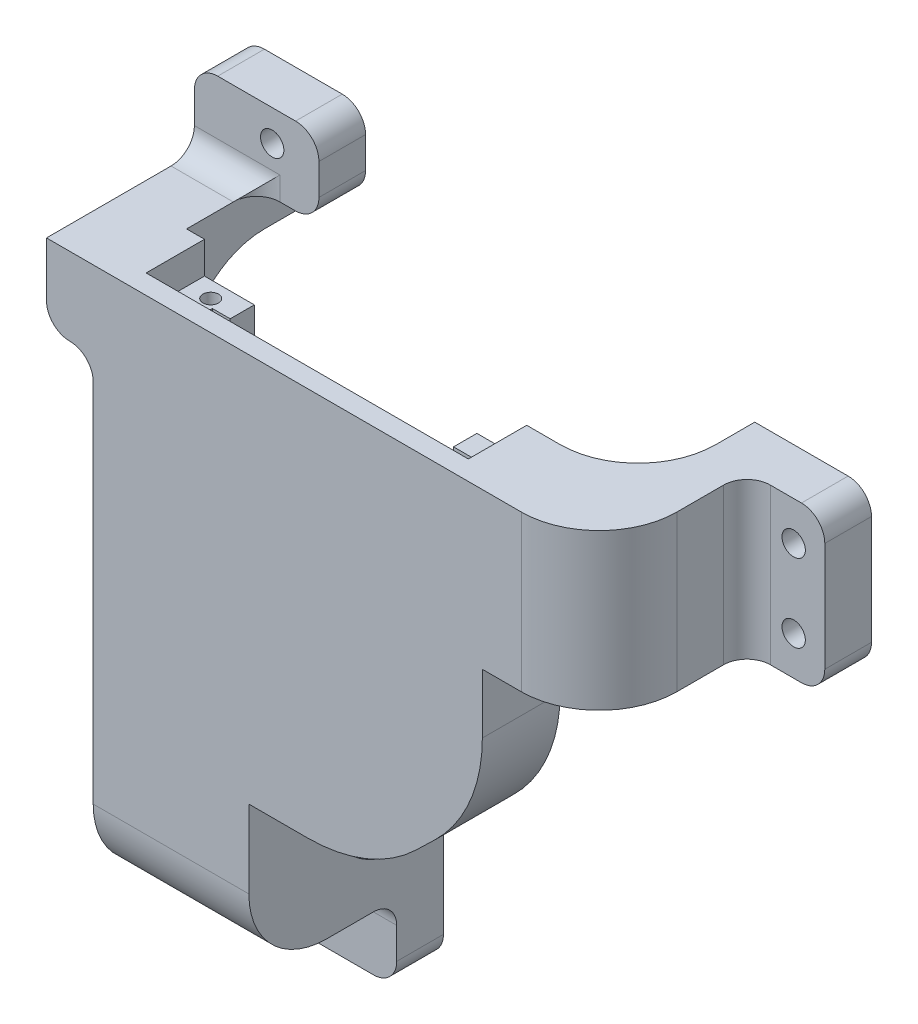
SolidWorks part; units mm, degrees
material "Polylactide (PLA)"
ref_plane "Front Plane" through (0, 0, 0) normal (0, 0, 1) x (1, 0, 0)
ref_plane "Top Plane" through (0, 0, 0) normal (0, 1, 0) x (1, 0, 0)
ref_plane "Right Plane" through (0, 0, 0) normal (1, 0, 0) x (0, 0, -1)
sketch "Sketch1" plane through (0, 0, 0) normal (0, 1, 0) x (1, 0, 0)
  line L0 (0, 0) -> (82.5, 0)
  line L1 (0, 0) -> (10, 0)
  line L2 (0, 0) -> (0, 20)
  line L3 (0, 20) -> (10, 20)
  line L4 (10, 0) -> (10, 20)
extrude "Boss-Extrude2" add sketch "Sketch1" along normal blind 10 contours L1 L4 L3 L2
sketch "Sketch3" plane through (0, 0, 0) normal (0, 1, 0) x (1, 0, 0)
  line L0 (0, 0) -> (82.5, 0)
  line L1 (0, 0) -> (10, 0) construction
  line L3 (82.5, 0) -> (72.5, 0)
  line L4 (82.5, 0) -> (82.5, 20)
  line L5 (82.5, 20) -> (72.5, 20)
  line L6 (72.5, 0) -> (72.5, 20)
extrude "Boss-Extrude3" add sketch "Sketch3" along normal blind 10 separate body contours L3 L6 L5 L4
sketch "Sketch4" plane through (0, 0, 0) normal (0, 1, 0) x (1, 0, 0)
  line L0 (10, 0) -> (10, 7.5)
  line L3 (10, 0) -> (10, 20) construction
  line L4 (72.5, 0) -> (72.5, 20) construction
  line L5 (10, 7.5) -> (72.5, 7.5)
  line L6 (10, 7.5) -> (10, 12.5)
  line L7 (10, 12.5) -> (72.5, 12.5)
  line L8 (72.5, 7.5) -> (72.5, 12.5)
extrude "Boss-Extrude4" add sketch "Sketch4" along normal blind 10 contours L5 L8 L7 L6
sketch "Sketch5" plane through (10, 0, 0) normal (1, 0, 0) x (0, 0, -1)
  line L0 (12.5, 0) -> (20, 10)
  line L1 (20, 0) -> (12.5, 10)
  line L2 (0, 10) -> (20, 10) construction
  circle A0 centre (16.25, 5) radius 0.5
sketch "Sketch6" plane through (10, 0, 0) normal (1, 0, 0) x (0, 0, -1)
  circle A0 centre (16.25, 5) radius 1
extrude "Cut-Extrude1" cut sketch "Sketch6" against normal blind 10
sketch "Sketch8" plane through (10, 0, 0) normal (1, 0, 0) x (0, 0, -1)
  line L0 (7.5, 0) -> (0, 10)
  line L1 (0, 10) -> (7.5, 10)
  line L2 (0, 10) -> (20, 10) construction
  line L3 (7.5, 10) -> (0, 0)
  circle A0 centre (3.75, 5) radius 1
sketch "Sketch10" plane through (72.5, 0, 0) normal (-1, 0, 0) x (0, 0, 1)
  circle A0 centre (-16.25, 5) radius 1
extrude "Cut-Extrude3" cut sketch "Sketch10" against normal blind 10 contours A0
sketch "Sketch11" plane through (0, 0, -12.5) normal (0, 0, -1) x (-1, 0, 0)
  line L0 (0, 10) -> (-35, 10)
  line L1 (-10, 10) -> (-72.5, 10) construction
  line L2 (-35, 10) -> (-35, 20)
  line L8 (-60, 45) -> (-10, 45)
  line L9 (-60, 45) -> (-60, -5)
  line L10 (-60, -5) -> (-10, -5)
  line L11 (-10, 45) -> (-10, -5)
  line L12 (-60, 45) -> (-10, -5) construction
  line L13 (-60, -5) -> (-10, 45) construction
sketch "Sketch16" plane through (10, 0, 0) normal (1, 0, 0) x (0, 0, -1)
  circle A0 centre (-1.6096, 5.0574) radius 1
sketch "Sketch17" plane through (72.5, 0, 0) normal (-1, 0, 0) x (0, 0, 1)
  circle A0 centre (-3.75, 5) radius 1
extrude "Boss-Extrude8" add sketch "Sketch11" against normal blind 10 contours L11 L10 L9 L8
sketch "Sketch18" plane through (0, 0, 0) normal (0, 0, 1) x (1, 0, 0)
  line L1 (0, 10) -> (10, 10)
  line L2 (0, 10) -> (0, 0)
  line L3 (0, 0) -> (10, 0)
  line L4 (10, 10) -> (10, 0)
extrude "Boss-Extrude9" add sketch "Sketch18" along normal blind 6
sketch "Sketch19" plane through (10, 0, 0) normal (1, 0, 0) x (0, 0, -1)
  circle A0 centre (-1.6096, 5.0574) radius 1
sketch "Sketch20" plane through (0, 0, 0) normal (0, -1, 0) x (1, 0, 0)
  line L0 (82.5, 0) -> (82.5, -20) construction
  line L1 (72.5, -12.5) -> (82.5, -12.5)
  line L2 (72.5, -12.5) -> (72.5, -2.5)
  line L3 (72.5, -2.5) -> (82.5, -2.5)
  line L4 (82.5, -12.5) -> (82.5, -2.5)
  line L5 (0, 6) -> (0, -20) construction
  line L6 (10, -2.5) -> (0, -2.5)
  line L7 (10, -2.5) -> (10, -12.5)
  line L8 (10, -12.5) -> (0, -12.5)
  line L9 (0, -2.5) -> (0, -12.5)
extrude "Boss-Extrude10" add sketch "Sketch20" along normal blind 12
sketch "Sketch21" plane through (72.5, 0, 0) normal (-1, 0, 0) x (0, 0, 1)
  circle A0 centre (-7.3635, -7.3831) radius 1
sketch "Sketch22" plane through (10, 0, 0) normal (1, 0, 0) x (0, 0, -1)
  circle A0 centre (7.5816, -8.9099) radius 1
sketch "Sketch23" plane through (0, 0, -12.5) normal (0, 0, -1) x (-1, 0, 0)
  line L0 (-60, 45) -> (-49.3, 45)
  line L3 (-60, 45) -> (-10, 45) construction
  line L5 (-49.3, 45) -> (-20.7, 45)
  line L6 (-49.3, 45) -> (-49.3, 0)
  line L7 (-49.3, 0) -> (-20.7, 0)
  line L8 (-20.7, 45) -> (-20.7, 0)
extrude "Cut-Extrude10" cut sketch "Sketch23" against normal blind 7.5 contours L6 L7 L8 L5
sketch "Sketch24" plane through (0, 45, 0) normal (0, 1, 0) x (1, 0, 0)
  line L1 (20.7, 12.5) -> (14.3, 12.5)
  line L2 (20.7, 12.5) -> (20.7, 5)
  line L3 (20.7, 5) -> (14.3, 5)
  line L4 (14.3, 12.5) -> (14.3, 5)
  line L5 (49.3, 12.5) -> (55.7, 12.5)
  line L6 (49.3, 12.5) -> (49.3, 5)
  line L7 (49.3, 5) -> (55.7, 5)
  line L8 (55.7, 12.5) -> (55.7, 5)
extrude "Cut-Extrude11" cut sketch "Sketch24" against normal blind 4.1
sketch "Sketch25" plane through (0, 40.9, 0) normal (0, 1, 0) x (1, 0, 0)
  line L1 (49.3, 5) -> (49.3, 7)
  line L2 (49.3, 5) -> (49.3, 12.5) construction
  line L4 (49.3, 7) -> (51.6, 7)
  line L5 (49.3, 7) -> (49.3, 9.5)
  line L6 (49.3, 9.5) -> (51.6, 9.5)
  line L7 (51.6, 7) -> (51.6, 9.5)
extrude "Cut-Extrude12" cut sketch "Sketch25" against normal blind 39 contours L4 L7 L6 L5
sketch "Sketch26" plane through (0, 40.9, 0) normal (0, 1, 0) x (1, 0, 0)
  line L0 (20.7, 5) -> (20.7, 7)
  line L1 (20.7, 5) -> (20.7, 12.5) construction
  line L3 (20.7, 7) -> (18.4, 7)
  line L4 (20.7, 7) -> (20.7, 9.4)
  line L5 (20.7, 9.4) -> (18.4, 9.4)
  line L6 (18.4, 7) -> (18.4, 9.4)
extrude "Cut-Extrude13" cut sketch "Sketch26" against normal blind 41 contours L3 L6 L5 L4
sketch "Sketch27" plane through (0, 40.9, 0) normal (0, 1, 0) x (1, 0, 0)
  line L1 (14.3, 12.5) -> (17.2, 12.5)
  line L2 (14.3, 12.5) -> (14.3, 10.4)
  line L3 (14.3, 10.4) -> (17.2, 10.4)
  line L4 (17.2, 12.5) -> (17.2, 10.4)
  circle A0 centre (17.2, 10.4) radius 1
extrude "Cut-Extrude14" cut sketch "Sketch27" against normal blind 10 contours A0
sketch "Sketch28" plane through (0, 40.9, 0) normal (0, 1, 0) x (1, 0, 0)
  line L1 (55.7, 12.5) -> (52.8, 12.5)
  line L2 (55.7, 12.5) -> (55.7, 10.4)
  line L3 (55.7, 10.4) -> (52.8, 10.4)
  line L4 (52.8, 12.5) -> (52.8, 10.4)
  circle A0 centre (52.8, 10.4) radius 1
extrude "Cut-Extrude15" cut sketch "Sketch28" against normal blind 10 contours A0
sketch "Sketch30" plane through (0, 40.9, 0) normal (0, 1, 0) x (1, 0, 0)
  line L0 (17.2, 10.4) -> (52.8, 10.4)
sketch "Sketch31" plane through (0, 0, -7.5) normal (0, 0, 1) x (1, 0, 0)
  line L4 (72.5, 10) -> (60, 10)
  line L5 (60, 10) -> (60, 0)
  line L6 (60, 0) -> (72.5, 0)
  line L7 (72.5, 0) -> (72.5, 10)
  line L8 (72.5, 10) -> (60, 10)
  line L9 (60, 10) -> (60, 0)
  line L10 (60, 0) -> (72.5, 0)
  line L11 (72.5, 0) -> (72.5, 10)
  dimension "D1" = 0
extrude "Boss-Extrude11" add sketch "Sketch31" along normal blind 5 contours L11 L8 L9 L10
sketch "Sketch32" plane through (0, 0, -20) normal (0, 0, -1) x (-1, 0, 0)
  line L4 (-82.5, 0) -> (-72.5, 0)
  line L5 (-72.5, 0) -> (-72.5, 10)
  line L6 (-72.5, 10) -> (-82.5, 10)
  line L7 (-82.5, 10) -> (-82.5, 0)
  line L8 (-82.5, 0) -> (-72.5, 0)
  line L9 (-72.5, 0) -> (-72.5, 10)
  line L10 (-72.5, 10) -> (-82.5, 10)
  line L11 (-82.5, 10) -> (-82.5, 0)
  dimension "D1" = 0
extrude "Cut-Extrude16" cut sketch "Sketch32" against normal blind 7.5
sketch3d "3DSketch1"
  line L4 (10, 0, -20) -> (0, 0, -20)
  line L5 (0, 0, -20) -> (0, 10, -20)
  line L6 (0, 10, -20) -> (10, 10, -20)
  line L7 (10, 10, -20) -> (10, 0, -20)
  line L8 (10, 0, -20) -> (0, 0, -20)
  line L9 (0, 0, -20) -> (0, 10, -20)
  line L10 (0, 10, -20) -> (10, 10, -20)
  line L11 (10, 10, -20) -> (10, 0, -20)
  dimension "D1" = 0
extrude "Cut-Extrude17" cut sketch "3DSketch1" along direction (0, 0, -1) on the side of the normal blind 7.5
sketch "Sketch33" plane through (0, -12, 0) normal (0, -1, 0) x (1, 0, 0)
  line L4 (10, -12.5) -> (10, -2.5)
  line L5 (10, -2.5) -> (0, -2.5)
  line L6 (0, -2.5) -> (0, -12.5)
  line L7 (0, -12.5) -> (10, -12.5)
  line L8 (10, -12.5) -> (10, -2.5)
  line L9 (10, -2.5) -> (0, -2.5)
  line L10 (0, -2.5) -> (0, -12.5)
  line L11 (0, -12.5) -> (10, -12.5)
  dimension "D1" = 0
extrude "Boss-Extrude12" add sketch "Sketch33" along normal blind 5
sketch "Sketch34" plane through (0, -12, 0) normal (0, -1, 0) x (1, 0, 0)
  line L4 (72.5, -2.5) -> (72.5, -12.5)
  line L5 (72.5, -12.5) -> (82.5, -12.5)
  line L6 (82.5, -12.5) -> (82.5, -2.5)
  line L7 (82.5, -2.5) -> (72.5, -2.5)
  line L8 (72.5, -2.5) -> (72.5, -12.5)
  line L9 (72.5, -12.5) -> (82.5, -12.5)
  line L10 (82.5, -12.5) -> (82.5, -2.5)
  line L11 (82.5, -2.5) -> (72.5, -2.5)
  dimension "D1" = 0
extrude "Boss-Extrude13" add sketch "Sketch34" along normal blind 5
sketch "Sketch35" plane through (0, 0, 6) normal (0, 0, 1) x (1, 0, 0)
  line L4 (0, 10) -> (0, 0)
  line L5 (0, 0) -> (10, 0)
  line L6 (10, 0) -> (10, 10)
  line L7 (10, 10) -> (0, 10)
  line L8 (0, 10) -> (0, 0)
  line L9 (0, 0) -> (10, 0)
  line L10 (10, 0) -> (10, 10)
  line L11 (10, 10) -> (0, 10)
  dimension "D1" = 0
extrude "Boss-Extrude14" add sketch "Sketch35" along normal blind 3.5
sketch "Sketch36" plane through (0, 0, 0) normal (0, 0, 1) x (1, 0, 0)
  line L4 (72.5, 0) -> (82.5, 0)
  line L5 (82.5, 0) -> (82.5, 10)
  line L6 (82.5, 10) -> (72.5, 10)
  line L7 (72.5, 10) -> (72.5, 0)
  line L8 (72.5, 0) -> (82.5, 0)
  line L9 (82.5, 0) -> (82.5, 10)
  line L10 (82.5, 10) -> (72.5, 10)
  line L11 (72.5, 10) -> (72.5, 0)
  dimension "D1" = 0
extrude "Boss-Extrude15" add sketch "Sketch36" along normal blind 9.5
sketch "Sketch37" plane through (10, 0, 0) normal (1, 0, 0) x (0, 0, -1)
  line L0 (-9.5, 10) -> (2.5, 0)
  line L1 (2.5, 0) -> (-9.5, 0)
  line L2 (-9.5, 0) -> (2.5, 10)
  circle A0 centre (-3.5, 5) radius 1.25
sketch "Sketch38" plane through (10, 0, 0) normal (1, 0, 0) x (0, 0, -1)
  line L0 (2.5, -5) -> (12.5, -17)
  line L1 (12.5, -17) -> (12.5, -5)
  line L2 (12.5, -5) -> (2.5, -17)
  circle A0 centre (7.5, -11) radius 1.25
extrude "Cut-Extrude18" cut sketch "Sketch37" against normal blind 15.5 and the other way blind 90.5 contours A0
extrude "Cut-Extrude19" cut sketch "Sketch38" against normal blind 15.5 and the other way blind 88.5 contours A0
sketch "Sketch39" plane through (0, 0, -12.5) normal (0, 0, -1) x (-1, 0, 0)
  line L0 (-60, 45) -> (-60, 10) construction
  line L1 (-60, 11.6104) -> (-89.9671, 11.6104)
  line L2 (-60, 11.6104) -> (-60, -20.2254)
  line L3 (-60, -20.2254) -> (-89.9671, -20.2254)
  line L4 (-89.9671, 11.6104) -> (-89.9671, -20.2254)
  line L5 (-10, 45) -> (-10, 10) construction
  line L6 (-10, 12.6125) -> (5.6172, 12.6125)
  line L7 (-10, 12.6125) -> (-10, -19.6858)
  line L8 (-10, -19.6858) -> (5.6172, -19.6858)
  line L9 (5.6172, 12.6125) -> (5.6172, -19.6858)
extrude "Cut-Extrude20" cut sketch "Sketch39" against normal blind 36
sketch "Sketch40" plane through (10, 0, 0) normal (-1, 0, 0) x (0, 0, 1)
  line L0 (-2.5, 45) -> (-2.5, -5) construction
  line L1 (-12.5, 45) -> (-2.5, 45)
  line L2 (-12.5, 45) -> (-12.5, 35)
  line L3 (-12.5, 35) -> (-2.5, 35)
  line L4 (-2.5, 45) -> (-2.5, 35)
extrude "Boss-Extrude16" add sketch "Sketch40" along normal blind 6
sketch "Sketch41" plane through (0, -5, 0) normal (0, -1, 0) x (1, 0, 0)
  line L1 (10, -2.5) -> (30, -2.5)
  line L2 (10, -2.5) -> (10, -12.5)
  line L3 (10, -12.5) -> (30, -12.5)
  line L4 (30, -2.5) -> (30, -12.5)
extrude "Boss-Extrude17" add sketch "Sketch41" along normal blind 20
sketch "Sketch43" plane through (60, 0, 0) normal (1, 0, 0) x (0, 0, -1)
  line L0 (2.5, 45) -> (12.5, 45) construction
  line L1 (2.5, 25) -> (12.5, 25)
  line L2 (2.5, 25) -> (2.5, 45)
  line L3 (2.5, 45) -> (12.5, 45)
  line L4 (12.5, 25) -> (12.5, 45)
  line L5 (2.5, 45) -> (2.5, -5) construction
  line L6 (12.5, 45) -> (12.5, -5) construction
extrude "Boss-Extrude18" add sketch "Sketch43" along normal blind 15
sketch "Sketch44" plane through (0, 0, -12.5) normal (0, 0, -1) x (-1, 0, 0)
  line L1 (-75, 45) -> (-70, 45)
  line L2 (-75, 45) -> (-75, 25)
  line L3 (-75, 25) -> (-70, 25)
  line L4 (-70, 45) -> (-70, 25)
  line L6 (-30, -25) -> (-10, -25)
  line L7 (-30, -25) -> (-30, -20)
  line L8 (-30, -20) -> (-10, -20)
  line L9 (-10, -25) -> (-10, -20)
  line L10 (-4, 45) -> (-12, 45)
  line L11 (-4, 45) -> (-4, 40)
  line L12 (-4, 40) -> (-12, 40)
  line L13 (-12, 45) -> (-12, 40)
extrude "Boss-Extrude19" add sketch "Sketch44" along normal blind 13
sketch "Sketch45" plane through (0, 0, -25.5) normal (0, 0, -1) x (-1, 0, 0)
  line L0 (-10, -20) -> (-30, -20) construction
  line L1 (-70, 45) -> (-85, 45)
  line L2 (-70, 45) -> (-70, 25)
  line L3 (-70, 25) -> (-85, 25)
  line L4 (-85, 45) -> (-85, 25)
  line L5 (-30, -20) -> (-10, -20)
  line L6 (-30, -20) -> (-30, -35)
  line L7 (-30, -35) -> (-10, -35)
  line L8 (-10, -20) -> (-10, -35)
  line L10 (-12, 40) -> (-4, 40)
  line L11 (-12, 40) -> (-12, 55)
  line L12 (-12, 55) -> (-4, 55)
  line L13 (-4, 40) -> (-4, 55)
extrude "Boss-Extrude20" add sketch "Sketch45" against normal blind 4
sketch "Sketch47" plane through (0, 0, -21.5) normal (0, 0, 1) x (1, 0, 0)
  line L0 (30, -35) -> (10, -35) construction
  line L1 (10, -35) -> (10, -25) construction
  line L2 (85, 25) -> (75, 25) construction
  line L3 (85, 45) -> (85, 25) construction
  circle A0 centre (15, -31) radius 1.5
  circle A2 centre (81, 30) radius 1.5
  circle A3 centre (81, 40) radius 1.5
  dimension "D1" = 4
  dimension "D5" = 5
  dimension "D2" = 5
  dimension "D6" = 4
  dimension "D7" = 10
  dimension "D8" = 0
sketch "Sketch49" plane through (0, 0, -25.5) normal (0, 0, -1) x (-1, 0, 0)
  line L0 (-4, 40) -> (-4, 55) construction
  line L1 (-4, 55) -> (-12, 55) construction
  line L2 (-12, 55) -> (-12, 40) construction
  line L3 (-12, 40) -> (-4, 40) construction
  line L4 (-30, -20) -> (-30, -35) construction
  line L5 (-30, -35) -> (-10, -35) construction
  line L6 (-10, -35) -> (-10, -20) construction
  line L7 (-10, -20) -> (-30, -20) construction
  line L8 (-70, 45) -> (-85, 45) construction
  line L9 (-85, 45) -> (-85, 25) construction
  line L10 (-85, 25) -> (-70, 25) construction
  line L11 (-70, 25) -> (-70, 45) construction
  line L12 (-4, 40) -> (-4, 55)
  line L13 (-4, 55) -> (-12, 55)
  line L14 (-12, 55) -> (-12, 40)
  line L15 (-12, 40) -> (-4, 40)
  line L16 (-30, -20) -> (-30, -35)
  line L17 (-30, -35) -> (-10, -35)
  line L18 (-10, -35) -> (-10, -20)
  line L19 (-10, -20) -> (-30, -20)
  line L20 (-70, 45) -> (-85, 45)
  line L21 (-85, 45) -> (-85, 25)
  line L22 (-85, 25) -> (-70, 25)
  line L23 (-70, 25) -> (-70, 45)
extrude "Boss-Extrude21" add sketch "Sketch49" along normal blind 2
extrude "Cut-Extrude22" cut sketch "Sketch47" against normal blind 10
fillet "Fillet1" radius 3 3 edges at (20, -25, -21.5) (8, 45, -21.5) (75, 35, -21.5)
fillet "Fillet2" radius 10 5 edges at (8, 40, -12.5) (20, -20, -12.5) (20, -25, -2.5) (75, 35, -2.5) (70, 35, -12.5)
sketch "Sketch48" plane through (0, 0, -12.5) normal (0, 0, -1) x (-1, 0, 0)
  line L0 (-64.4149, 10.6529) -> (-62.6737, 7.2794)
  line L1 (-41.1264, -9.3708) -> (-66.809, 15.4412)
  line L2 (-66.809, 15.4412) -> (-67.7885, -8.0649)
  line L3 (-67.7885, -8.0649) -> (-41.1264, -9.3708)
extrude "Cut-Extrude23" cut sketch "Sketch48" against normal up to surface (10 mm away)
fillet "Fillet3" radius 20 2 edges at (45.6506, -5, -7.5) (60, 8.863, -7.5)
fillet "Fillet7" radius 3 2 edges at (10, 35, -8.1699) (4, 35, -8.1699)
fillet "Fillet8" radius 3 5 edges at (10, -35, -24.5) (30, -35, -24.5) (85, 25, -24.5) (85, 45, -24.5) (4, 55, -24.5)
sketch "Sketch50" plane through (12, 0, 0) normal (1, 0, 0) x (0, 0, -1)
  line L1 (21.5, 55) -> (27.5, 55)
  line L2 (21.5, 55) -> (21.5, 45)
  line L3 (21.5, 45) -> (27.5, 45)
  line L4 (27.5, 55) -> (27.5, 45)
extrude "Boss-Extrude22" add sketch "Sketch50" along normal blind 8
sketch "Sketch46" plane through (0, 0, -21.5) normal (0, 0, 1) x (1, 0, 0)
  line L0 (4, 48) -> (4, 52) construction
  line L2 (7, 55) -> (20, 55) construction
  circle A0 centre (14, 51) radius 1.5
  dimension "D1" = 10
  dimension "D2" = 4
extrude "Cut-Extrude21" cut sketch "Sketch46" against normal blind 10
fillet "Fillet10" radius 3 3 edges at (12, 46.5, -21.5) (20, 45, -24.5) (20, 55, -24.5)
